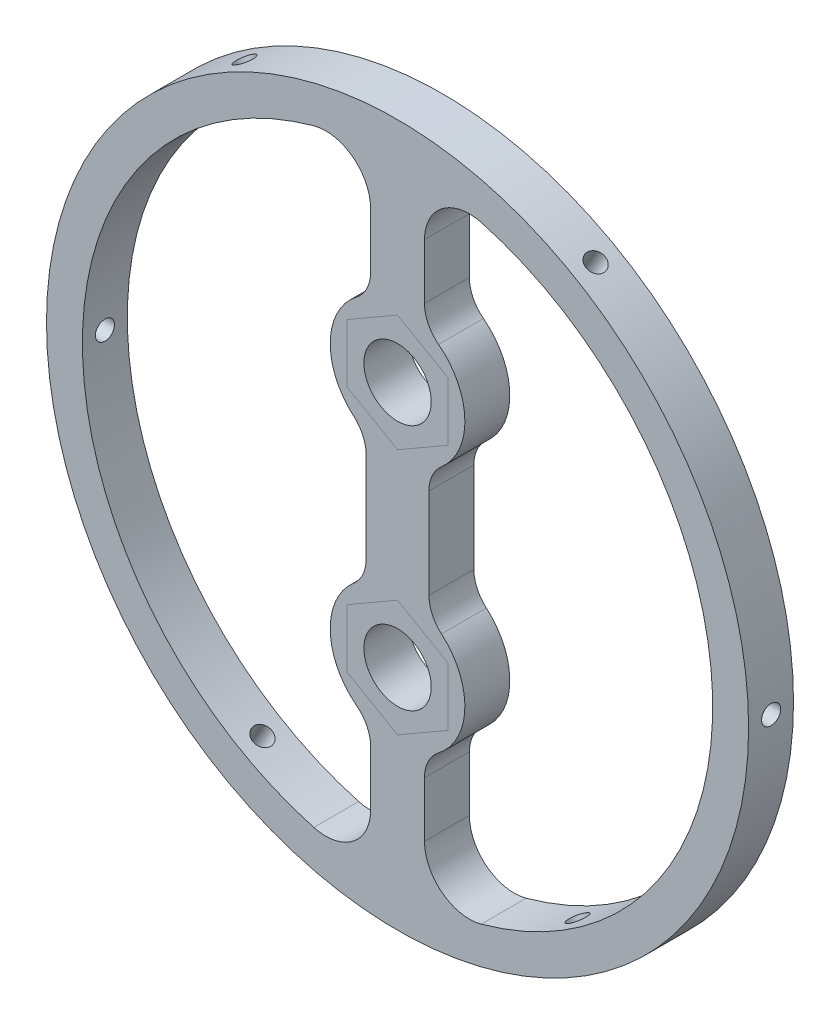
SolidWorks part; units mm, degrees
note: '?' marks a value the reader was unsure of.
material "6061-T6 (SS)"
ref_plane "Front Plane" through (0, 0, 0) normal (0, 0, 1) x (1, 0, 0)
ref_plane "Top Plane" through (0, 0, 0) normal (0, 1, 0) x (1, 0, 0)
ref_plane "Right Plane" through (0, 0, 0) normal (1, 0, 0) x (0, 0, -1)
sketch "Sketch1" plane through (0, 0, 0) normal (0, 0, 1) x (1, 0, 0)
  circle A0 centre (0, 0) radius 49.657
  dimension "D1" = 99.314
extrude "Boss-Extrude1" add sketch "Sketch1" along normal blind 6.35
ref_axis "Axis1" through (0, 0, 35.2807) along (0, 0, -1)?
sketch "Sketch3" plane through (0, 0, 6.35) normal (0, 0, 1) x (1, 0, 0)
  line L2 (0, 0) -> (0, 49.657) construction
  line L3 (0, 0) -> (0, -49.657) construction
  line L10 (-49.657, 0) -> (49.657, 0) construction
  line L11 (-3.81, 44.4139) -> (-3.81, 26.1923)
  line L12 (3.81, 44.4139) -> (3.81, 26.1923)
  line L13 (-4.445, 0) -> (-44.577, 0)
  line L14 (4.445, 0) -> (44.577, 0)
  line L15 (-4.445, 9.0383) -> (-4.445, -9.0383)
  line L16 (4.445, 9.0383) -> (4.445, -9.0383)
  line L17 (3.81, -44.4139) -> (3.81, -26.1923)
  line L18 (-3.81, -44.4139) -> (-3.81, -26.1923)
  arc A0 (-3.81, 44.4139) -> (-3.81, -44.4139) centre (0, 0) ccw
  circle A2 centre (0, 0) radius 49.657 construction
  arc A7 (3.81, -44.4139) -> (3.81, 44.4139) centre (0, 0) ccw
  arc A9 (-3.81, 26.1923) -> (-4.445, 9.0383) centre (0, 17.4625) ccw
  arc A10 (4.445, 9.0383) -> (3.81, 26.1923) centre (0, 17.4625) ccw
  arc A11 (4.445, -9.0383) -> (3.81, -26.1923) centre (0, -17.4625) cw
  arc A12 (-3.81, -26.1923) -> (-4.445, -9.0383) centre (0, -17.4625) cw
  point P18 (0, 0)
  dimension "D7" = 19.05
  dimension "D2" = 180
  dimension "D5" = 5.08
  dimension "D1" = 34.925
  dimension "D3" = 7.62
  dimension "D4" = 3.81
  dimension "D6" = 8.89
  dimension "D8" = 4.445
extrude "Cut-Extrude1" cut sketch "Sketch3" against normal through all contours A0 L18 A12 L15 A9 L11 | L16 A11 L17 A7 L12 A10
fillet "Fillet1" radius 6.35 4 edges at (-3.81, 44.4139, 3.175) (-3.81, -44.4139, 3.175) (3.81, -44.4139, 3.175) (3.81, 44.4139, 3.175)
fillet "Fillet2" radius 5.08 8 edges at (3.81, 26.1923, 3.175) (-3.81, 26.1923, 3.175) (4.445, 9.0383, 3.175) (-4.445, 9.0383, 3.175) (-4.445, -9.0383, 3.175) (4.445, -9.0383, 3.175) (3.81, -26.1923, 3.175) (-3.81, -26.1923, 3.175)
sketch "Sketch4" plane through (0, 0, 6.35) normal (0, 0, 1) x (1, 0, 0)
  circle A1 centre (0, 17.4625) radius 4.7625
  circle A2 centre (0, 17.4625) radius 9.525 construction
  circle A3 centre (0, -17.4625) radius 9.525 construction
  arc A4 (-6.212, -10.2419) -> (-5.7978, -25.0197) centre (0, -17.4625) ccw construction
  circle A5 centre (0, -17.4625) radius 4.7625
  dimension "D1" = 9.525
extrude "Cut-Extrude2" cut sketch "Sketch4" against normal through all
sketch "Sketch5" plane through (0, 0, 6.35) normal (0, 0, 1) x (1, 0, 0)
  line L0 (0, 49.657) -> (0, -49.657) construction
  line L1 (7.1438, 21.5869) -> (0, 25.7114)
  line L2 (0, 25.7114) -> (-7.1437, 21.5869)
  line L3 (-7.1437, 21.5869) -> (-7.1437, 13.3381)
  line L4 (-7.1437, 13.3381) -> (0, 9.2136)
  line L5 (0, 9.2136) -> (7.1438, 13.3381)
  line L6 (7.1438, 13.3381) -> (7.1438, 21.5869)
  line L7 (7.1437, -13.3381) -> (0, -9.2136)
  line L8 (0, -9.2136) -> (-7.1438, -13.3381)
  line L9 (-7.1438, -13.3381) -> (-7.1437, -21.5869)
  line L10 (-7.1437, -21.5869) -> (0, -25.7114)
  line L11 (0, -25.7114) -> (7.1438, -21.5869)
  line L12 (7.1438, -21.5869) -> (7.1437, -13.3381)
  circle A0 centre (0, 17.4625) radius 7.1438 construction
  circle A1 centre (0, -17.4625) radius 7.1438 construction
  circle A2 centre (0, 0) radius 49.657 construction
  point P10 (0, 0)
  point P26 (0, -49.657)
  point P27 (5.7117, 14.6877)
  dimension "D1" = 14.2875
  dimension "D2" = 14.2875
split line "Split Line1"
hole_wizard "#6-32 Tapped Hole1" positions "3DSketch4" profile "Sketch9" tap size "#6-32" standard "DME"
sketch3d "3DSketch4"
  line L0 (0, 0, 0) -> (0, 0, 6.35) construction
  line L1 (0, 0, 6.35) -> (0, 0, 0) construction
  point P0 (49.657, -0.0026, 3.1664)
  point P22 (0, 0, 0)
  point P23 (0, 0, 0)
  point P24 (0, 0, 3.2192)
  point P25 (0, 0, 0)
  point P26 (0, 0, 0)
  point P27 (0.3221, -49.656, 3.2758)
  point P28 (0, 0, 0)
  point P29 (0.0341, -49.657, 3.319)
  point P30 (0, 0, 0)
  point P31 (49.6569, -0.1034, 1.079)
  point P32 (49.657, -0.0027, 3.0185)
  point P33 (49.657, -0.0284, 5.2783)
  point P34 (49.657, 0.0101, 5.0857)
  point P35 (22.7109, -44.1592, 0.264)
  point P36 (-4.1497, -49.4833, 5.3291)
  point P37 (0.0042, -49.657, 4.9284)
  point P38 (49.5537, 3.2012, 0.6499)
  point P39 (49.657, -0.0026, 3.1664)
cosmetic thread "Hole Thread1" parameters "D1"=9.652, "D2"=3.5052
sketch "Sketch9" plane through (49.657, -0.0026, 3.1664) normal (0, 0, 1) x (0.0001, 1, 0)
  line L0 (0, 0) -> (0, 13.5127)
  line L1 (0, 13.5127) -> (1.3525, 12.7)
  line L2 (1.3525, 12.7) -> (1.3525, 0)
  line L5 (1.3525, 0) -> (0, 0)
  line L10 (0, 13.5127) -> (-1.3526, 12.7) construction
  line L11 (0, -6.35) -> (0, 107.95) construction
  dimension "Tap Drill Dia." = 2.7051
  dimension "Tap Drill Depth" = 12.7
  dimension "Drill Angle" = 118
pattern_circular "CirPattern1" count 6 over 360 about axis through (0, 0, 6.35) along (0, 0, -1) of "#6-32 Tapped Hole1"
cosmetic thread "Hole Thread2" parameters "D1"=9.652, "D2"=3.5052
cosmetic thread "Hole Thread3" parameters "D1"=9.652, "D2"=3.5052
cosmetic thread "Hole Thread4" parameters "D1"=9.652, "D2"=3.5052
cosmetic thread "Hole Thread5" parameters "D1"=9.652, "D2"=3.5052
cosmetic thread "Hole Thread6" parameters "D1"=9.652, "D2"=3.5052
equation "\"D4@Sketch3\"=\"D3@Sketch3\"/2"
equation "\"D8@Sketch3\"=\"D6@Sketch3\"/2"
equation "\"D2@Sketch5\"=\"D1@Sketch5\""
